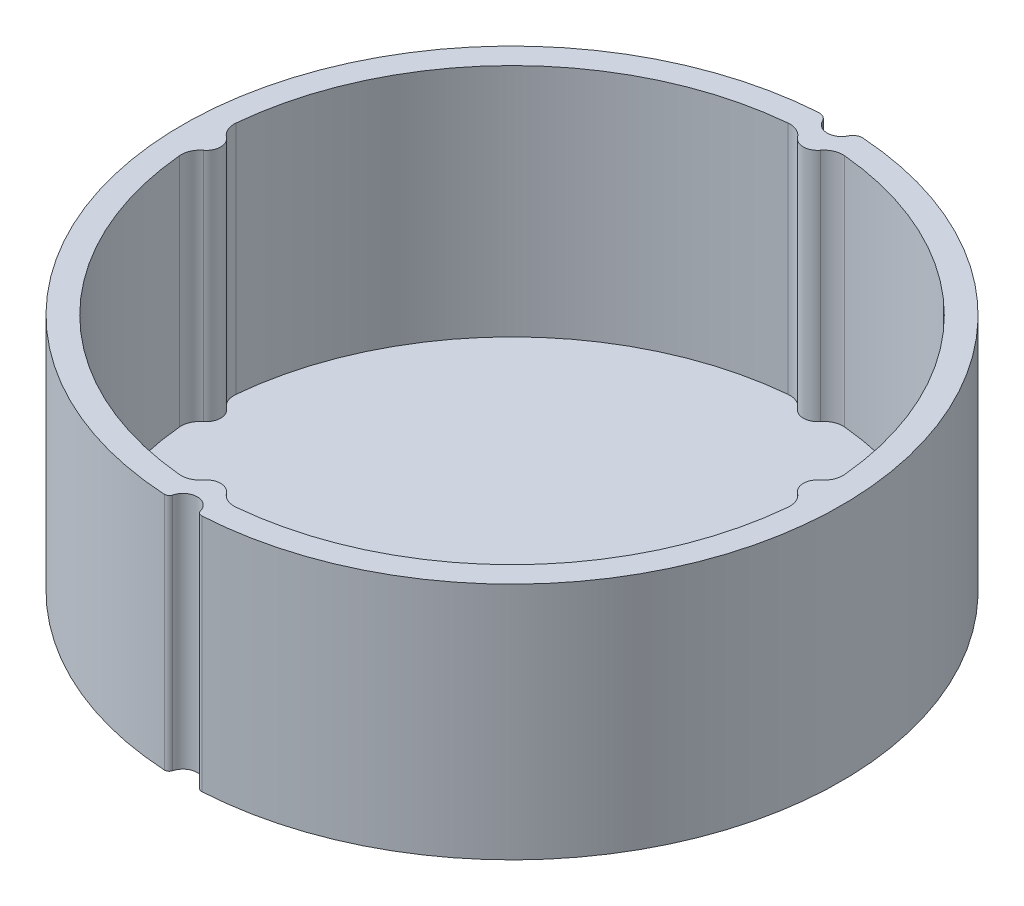
SolidWorks part; units mm, degrees
ref_plane "Front Plane" through (0, 0, 0) normal (0, 0, 1) x (1, 0, 0)
ref_plane "Top Plane" through (0, 0, 0) normal (0, 1, 0) x (1, 0, 0)
ref_plane "Right Plane" through (0, 0, 0) normal (1, 0, 0) x (0, 0, -1)
sketch "Sketch1" plane through (0, 0, 0) normal (0, 1, 0) x (1, 0, 0)
  line L3 (0, 0.002) -> (0, 3.7877) construction
  line L4 (0, 3.7877) -> (2.417, 3.7877)
  line L5 (0, 3.7877) -> (-2.417, 3.7877)
  arc A0 (1.9642, -34.442) -> (34.1982, 4.5552) centre (0, 0.002) ccw
  arc A2 (-2.417, 3.7877) -> (2.417, 3.7877) centre (0, 0.002) ccw
  circle A3 centre (0, 0.002) radius 34.5 construction
  arc A7 (-1.3541, 33.8562) -> (1.3541, 33.8562) centre (0, 34.5015) ccw
  arc A8 (34.1982, 4.5552) -> (2.3241, 34.4236) centre (0, 0.002) ccw
  arc A9 (-2.3241, 34.4236) -> (-34.1982, 4.5552) centre (0, 0.002) ccw
  arc A10 (-34.1982, 4.5552) -> (-1.9642, -34.442) centre (0, 0.002) ccw
  arc A11 (1.3541, 33.8562) -> (2.3241, 34.4236) centre (2.2568, 33.4259) cw
  arc A12 (-1.3541, 33.8562) -> (-2.3241, 34.4236) centre (-2.2568, 33.4259) ccw
  arc A13 (1.4518, -34.0686) -> (-1.4518, -34.0686) centre (0, -34.4457) ccw
  arc A14 (1.4518, -34.0686) -> (1.9642, -34.442) centre (1.9358, -33.9428) ccw
  arc A15 (-1.4518, -34.0686) -> (-1.9642, -34.442) centre (-1.9358, -33.9428) cw
  point P15 (1.4997, 34.4694)
  dimension "D2" = 4.834
  dimension "D3" = 4.4915
  dimension "D4" = 34.5
  dimension "D5" = 1
  dimension "D6" = 1.5
  dimension "D7" = 0.5
  dimension "D11" = 1.4997
sketch "Sketch2" plane through (0, 0, 0) normal (0, 1, 0) x (1, 0, 0)
  arc A0 (-31.8625, -2.9633) -> (-2.9633, -31.8625) centre (0, 0) ccw
  arc A1 (-1.1906, 31.0876) -> (1.1906, 31.0876) centre (0, 32) ccw
  arc A2 (31.0876, 1.1906) -> (31.0876, -1.1906) centre (32, 0) ccw
  arc A3 (1.1906, -31.0876) -> (-1.1906, -31.0876) centre (0, -32) ccw
  arc A4 (-31.0876, -1.1906) -> (-31.0876, 1.1906) centre (-32, 0) ccw
  arc A5 (-2.9633, 31.8625) -> (-31.8625, 2.9633) centre (0, 0) ccw
  arc A6 (31.8625, 2.9633) -> (2.9633, 31.8625) centre (0, 0) ccw
  arc A7 (2.9633, -31.8625) -> (31.8625, -2.9633) centre (0, 0) ccw
  arc A8 (-31.0876, -1.1906) -> (-31.8625, -2.9633) centre (-29.8711, -2.7781) ccw
  arc A9 (-31.0876, 1.1906) -> (-31.8625, 2.9633) centre (-29.8711, 2.7781) cw
  arc A10 (1.1906, -31.0876) -> (2.9633, -31.8625) centre (2.7781, -29.8711) ccw
  arc A11 (-1.1906, -31.0876) -> (-2.9633, -31.8625) centre (-2.7781, -29.8711) cw
  arc A12 (31.0876, 1.1906) -> (31.8625, 2.9633) centre (29.8711, 2.7781) ccw
  arc A13 (31.0876, -1.1906) -> (31.8625, -2.9633) centre (29.8711, -2.7781) cw
  arc A14 (1.1906, 31.0876) -> (2.9633, 31.8625) centre (2.7781, 29.8711) cw
  arc A15 (-1.1906, 31.0876) -> (-2.9633, 31.8625) centre (-2.7781, 29.8711) ccw
  point P21 (1.4996, -31.9648)
  point P26 (31.9648, 1.4996)
  point P33 (-1.4996, 31.9648)
  dimension "D1" = 32
  dimension "D2" = 1.5
  dimension "D3" = 1.5
  dimension "D4" = 1.5
  dimension "D5" = 1.5
  dimension "D6" = 2
extrude "Boss-Extrude1" add sketch "Sketch1" along normal blind 25 contours A10 A0 A8 A7 A9 A2 L5 L4 region at (2.2155, 0, 33.5591)
extrude "Cut-Extrude2" cut sketch "Sketch2" along normal through all
extrude "Boss-Extrude2" add sketch "Sketch2<2>" along normal blind 0.4
sketch "Sketch2<2>" plane through (0, 0, 0) normal (0, 1, 0) x (1, 0, 0) same geometry as "Sketch2"
